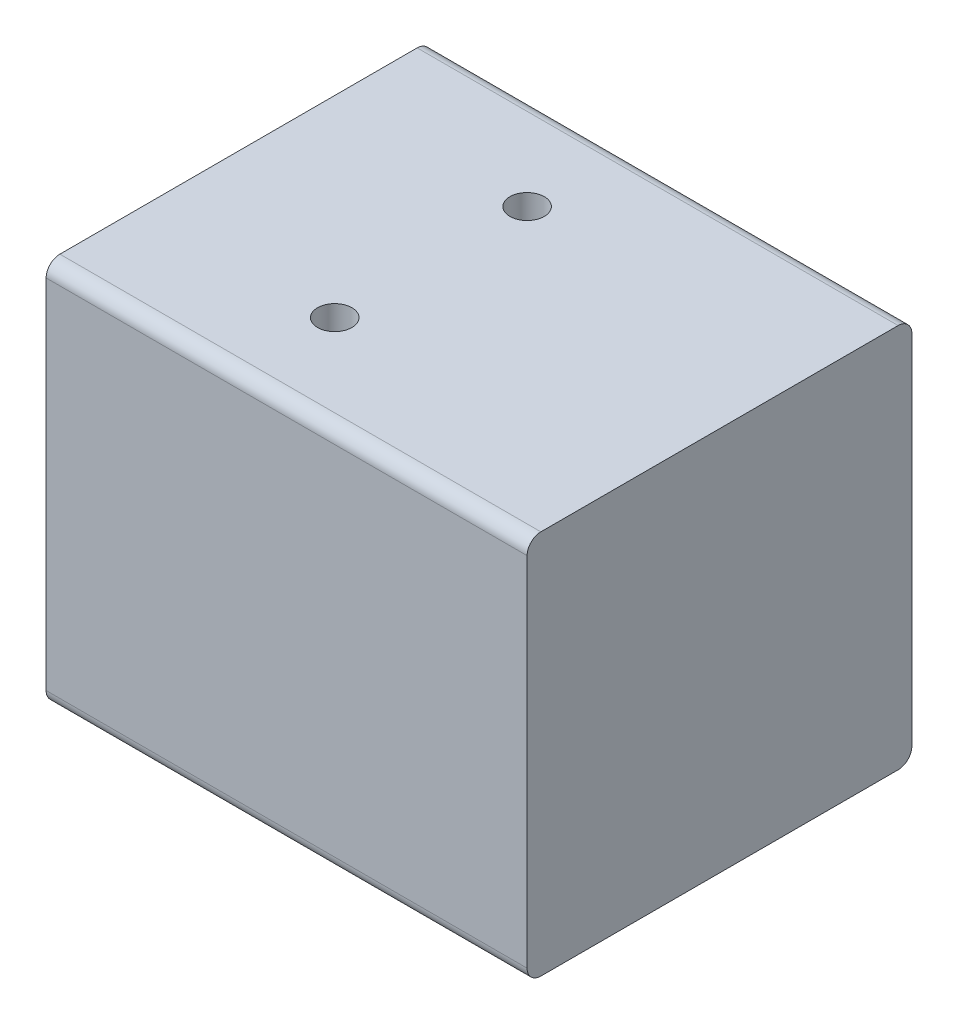
SolidWorks part; units mm, degrees
material "Pine"
ref_plane "Front Plane" through (0, 0, 0) normal (0, 0, 1) x (1, 0, 0)
ref_plane "Top Plane" through (0, 0, 0) normal (0, 1, 0) x (1, 0, 0)
ref_plane "Right Plane" through (0, 0, 0) normal (1, 0, 0) x (0, 0, -1)
sketch "Sketch1" plane through (0, 0, 0) normal (0, 0, 1) x (1, 0, 0)
  line L1 (-55.5625, 88.9) -> (55.5625, 88.9)
  line L2 (-55.5625, 88.9) -> (-55.5625, 0)
  line L3 (-55.5625, 0) -> (55.5625, 0)
  line L4 (55.5625, 88.9) -> (55.5625, 0)
  point P4 (0, 0)
  dimension "D1" = 111.125
  dimension "D2" = 88.9
extrude "Boss-Extrude1" add sketch "Sketch1" along normal blind 88.9
fillet "Fillet1" radius 3.175 4 edges at (0, 0, 0) (0, 0, 88.9) (0, 88.9, 0) (0, 88.9, 88.9)
sketch "Sketch5" plane through (0, 88.9, 0) normal (0, 1, 0) x (1, 0, 0)
  line L0 (-55.5625, -44.45) -> (55.5625, -44.45) construction
  line L1 (-55.5625, -85.725) -> (-55.5625, -3.175) construction
  line L2 (-11.1125, -22.225) -> (-11.1125, -66.675) construction
  line L3 (55.5625, -85.725) -> (55.5625, -3.175) construction
  point P4 (0, 0)
  point P7 (-11.1125, -44.45)
  dimension "D1" = 44.45
  dimension "D2" = 44.45
hole_wizard "5/16 (0.3125) Diameter Hole1" positions "Sketch6" profile "Sketch7" hole size "5/16" standard "ANSI Inch" end condition up to next
sketch "Sketch6" plane through (0, 88.9, 0) normal (0, 1, 0) x (1, 0, 0)
  point P0 (-11.1125, -22.225)
  point P3 (-11.1125, -66.675)
sketch "Sketch7" plane through (-11.1125, 88.9, 22.225) normal (1, 0, 0) x (0, 0, 1)
  line L0 (0, 0) -> (0, 88.9)
  line L1 (0, 88.9) -> (3.9687, 88.9)
  line L2 (3.9687, 88.9) -> (3.9687, 0)
  line L5 (3.9687, 0) -> (0, 0)
  line L11 (0, -6.35) -> (0, 107.95) construction
  dimension "Thru Hole Dia." = 7.9375
  dimension "Thru Hole Depth" = 88.9
ref_axis "Axis1" through (-11.1125, 0, 22.225) along (0, 1, 0)
ref_axis "Axis2" through (-11.1125, 0, 66.675) along (0, 1, 0)
